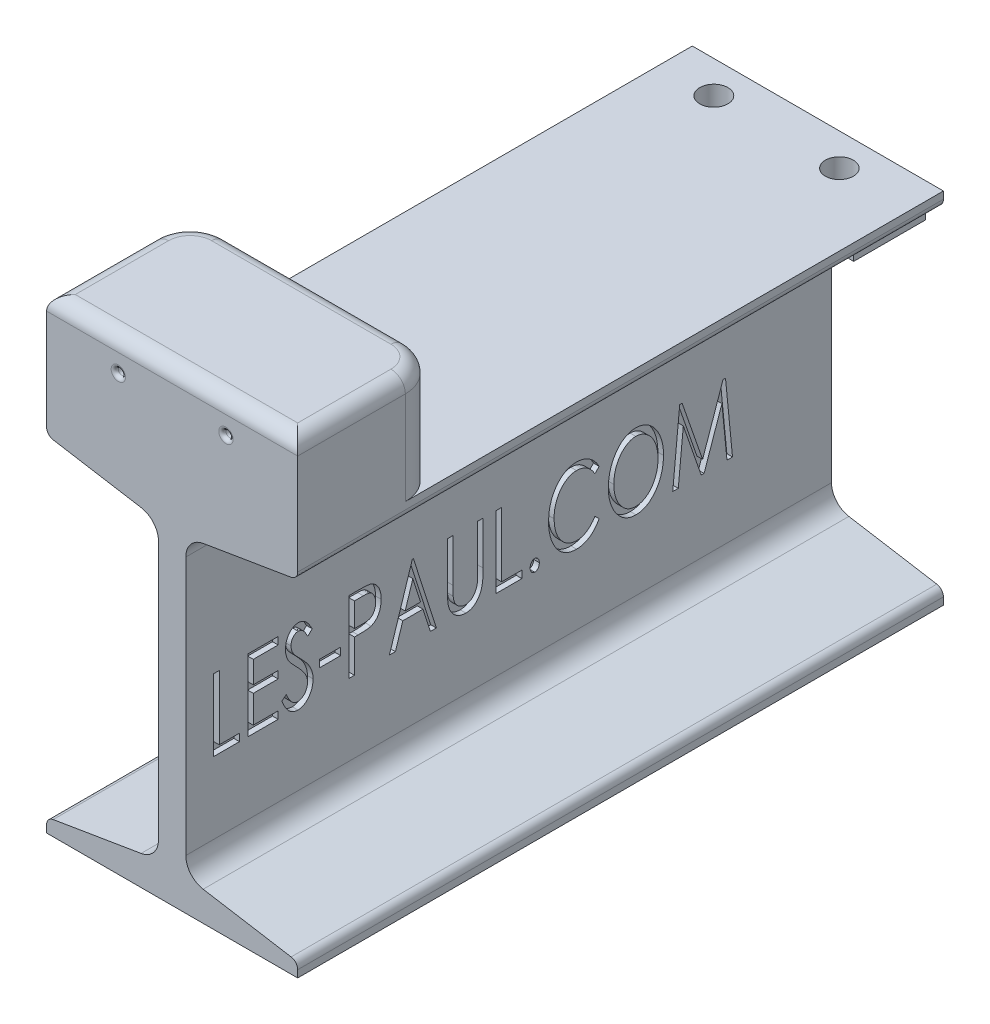
SolidWorks part; units mm, degrees
note: The reader was unsure of these and kept them because the rebuilt part matched: shared geometry of "Sketch47<4>".
material "AISI 1010 Steel, hot rolled bar"
ref_plane "Front Plane" through (0, 0, 0) normal (0, 0, 1) x (1, 0, 0)
ref_plane "Top Plane" through (0, 0, 0) normal (0, 1, 0) x (1, 0, 0)
ref_plane "Right Plane" through (0, 0, 0) normal (1, 0, 0) x (0, 0, -1)
sketch "Sketch1" plane through (0, 0, 0) normal (0, 0, 1) x (1, 0, 0)
  line L0 (0, -63.5) -> (0, 63.5) construction
  line L1 (-44.45, 63.5) -> (44.45, 63.5)
  line L2 (44.45, 63.5) -> (44.45, 60.96)
  line L3 (42.1152, 58.204) -> (10.9813, 53.0163)
  line L4 (4.826, 45.7505) -> (4.826, -45.7505)
  line L5 (10.9813, -53.0163) -> (42.1152, -58.204)
  line L6 (44.45, -60.96) -> (44.45, -63.5)
  line L7 (44.45, -63.5) -> (-44.45, -63.5)
  line L8 (-44.45, -60.96) -> (-44.45, -63.5)
  line L9 (-10.9813, -53.0163) -> (-42.1152, -58.204)
  line L10 (-4.826, 45.7505) -> (-4.826, -45.7505)
  line L11 (-42.1152, 58.204) -> (-10.9813, 53.0163)
  line L12 (-44.45, 63.5) -> (-44.45, 60.96)
  arc A0 (42.1152, -58.204) -> (44.45, -60.96) centre (41.656, -60.96) cw
  arc A1 (44.45, 60.96) -> (42.1152, 58.204) centre (41.656, 60.96) cw
  arc A2 (4.826, -45.7505) -> (10.9813, -53.0163) centre (12.192, -45.7505) ccw
  arc A3 (10.9813, 53.0163) -> (4.826, 45.7505) centre (12.192, 45.7505) ccw
  arc A4 (-10.9813, 53.0163) -> (-4.826, 45.7505) centre (-12.192, 45.7505) cw
  arc A5 (-4.826, -45.7505) -> (-10.9813, -53.0163) centre (-12.192, -45.7505) cw
  arc A6 (-44.45, 60.96) -> (-42.1152, 58.204) centre (-41.656, 60.96) ccw
  arc A7 (-42.1152, -58.204) -> (-44.45, -60.96) centre (-41.656, -60.96) ccw
  point P4 (0, 0)
  dimension "D3" = 2.794
  dimension "D4" = 7.366
  dimension "D1" = 127
  dimension "D2" = 44.45
  dimension "D5" = 9.46
  dimension "D6" = 9.46
  dimension "D7" = 2.54
  dimension "D8" = 2.54
  dimension "D9" = 4.826
extrude "Boss-Extrude1" add sketch "Sketch1" along normal mid plane 228.6
sketch "Sketch2" plane through (0, 63.5, 0) normal (0, 1, 0) x (1, 0, 0)
  line L0 (-44.45, -114.3) -> (-44.45, -63.5)
  line L1 (-44.45, -114.3) -> (-44.45, 114.3) construction
  line L2 (-44.45, -63.5) -> (44.45, -63.5)
  line L3 (44.45, -114.3) -> (44.45, 114.3) construction
  line L4 (44.45, -63.5) -> (44.45, -114.3)
  line L5 (44.45, -114.3) -> (-44.45, -114.3)
  dimension "D1" = 50.8
extrude "Boss-Extrude2" add sketch "Sketch2" along normal blind 38.1
fillet "Fillet4" radius 12.7 2 edges at (-44.45, 82.55, 63.5) (44.45, 82.55, 63.5)
fillet "Fillet5" radius 5.08 6 edges at (40.7303, 101.6, 67.2197) (0, 101.6, 63.5) (-40.7303, 101.6, 67.2197) (-44.45, 101.6, 95.25) (0, 101.6, 114.3) (44.45, 101.6, 95.25)
sketch "Sketch24" plane through (0, 0, 0) normal (0, 0, 1) x (1, 0, 0)
  line L0 (-10.9813, 53.0163) -> (-43.3872, 53.0163) construction
ref_plane "Plane2" through (0, 53.0163, 0) normal (0, 1, 0) x (1, 0, 0)
ref_plane "Plane4" through (0, -11.6213, 43.3713) normal (0, 0.2588, -0.9659) x (-1, 0, 0)
sketch "Sketch42" plane through (0, 141.2713, 63.5) normal (0, 0, 1) x (-1, 0, 0)
  line L0 (31.75, 44.7513) -> (-31.75, 44.7513) construction
  line L1 (44.45, 44.7513) -> (44.45, 77.7713) construction
  line L2 (0, 77.7713) -> (0, 44.7513) construction
  line L3 (-31.75, 77.7713) -> (31.75, 77.7713) construction
  circle A0 centre (19.05, 51.1013) radius 1.27
  circle A1 centre (-19.05, 51.1013) radius 1.27
  dimension "D1" = 2.54
  dimension "D3" = 6.35
  dimension "D2" = 25.4
extrude "Cut-Extrude3" cut sketch "Sketch42" against normal mid plane 177.8
fillet "Fillet8" radius 1.27 2 edges at (-20.32, 90.17, 114.3) (17.78, 90.17, 114.3)
sketch "Sketch45" plane through (0, 63.5, 0) normal (0, 1, 0) x (1, 0, 0)
  line L0 (-38.1, 114.3) -> (-38.1, 88.9)
  line L1 (44.45, 114.3) -> (-44.45, 114.3) construction
  line L2 (-38.1, 88.9) -> (38.1, 88.9)
  line L3 (38.1, 88.9) -> (38.1, 114.3)
  line L4 (38.1, 114.3) -> (-38.1, 114.3)
  line L5 (44.45, -76.2) -> (44.45, 114.3) construction
  line L6 (-44.45, -76.2) -> (-44.45, 114.3) construction
  dimension "D1" = 6.35
  dimension "D2" = 25.4
  dimension "D3" = 6.35
extrude "Boss-Extrude3" add sketch "Sketch45" against normal blind 12.065
sketch "Sketch47" plane through (0, 63.5, 0) normal (0, 1, 0) x (1, 0, 0)
  line L0 (0, 162.8047) -> (0, -29.721) construction
  line L1 (44.45, 114.3) -> (-44.45, 114.3) construction
  line L2 (-44.45, -76.2) -> (-44.45, 114.3) construction
  circle A0 centre (-25.4, 102.87) radius 5
  circle A2 centre (19.05, 102.87) radius 4.953
  dimension "D1" = 10
  dimension "D4" = 9.906
  dimension "D2" = 11.43
  dimension "D3" = 19.05
  dimension "D5" = 19.05
  dimension "D6" = 11.43
extrude "Cut-Extrude5" cut sketch "Sketch47" against normal up to surface (12.065 mm away) up to face at (22.8038, 51.435, -101.6)
sketch "Sketch51" plane through (4.826, 0, 0) normal (1, 0, 0) x (0, 0, -1)
  line L0 (-114.3, -45.7505) -> (-114.3, 45.7505) construction
  line L1 (-114.3, -45.7505) -> (114.3, -45.7505) construction
  text T0 "LES-PAUL.COM" font "Century Gothic" height 25.4
  dimension "D1" = 7.62
  dimension "D2" = 25.4
extrude "Cut-Extrude9" cut sketch "Sketch47<4>" against normal blind 25.4
sketch "Sketch47<4>" plane through (0, 63.5, 0) normal (0, 1, 0) x (1, 0, 0) same geometry as "Sketch47"
extrude "Cut-Extrude8" cut sketch "Sketch51" against normal blind 2
sketch "Sketch52" plane through (0, 51.435, 0) normal (0, -1, 0) x (1, 0, 0)
  line L0 (44.45, -114.3) -> (-44.45, -114.3) construction
  circle A0 centre (31.242, -102.87) radius 1.905
  circle A1 centre (19.05, -102.87) radius 4.953 construction
  dimension "D2" = 3.81
  dimension "D1" = 12.192
  dimension "D3" = 11.43
extrude "Cut-Extrude10" cut sketch "Sketch52" against normal blind 8.89
sketch "Sketch53" plane through (0, 51.435, 0) normal (0, -1, 0) x (1, 0, 0)
  line L0 (-7.5075, -114.3) -> (-38.1, -114.3) construction
  circle A0 centre (-13.208, -102.87) radius 1.905
  circle A1 centre (-25.4, -102.87) radius 5 construction
  dimension "D1" = 3.81
  dimension "D2" = 12.192
  dimension "D3" = 11.43
extrude "Cut-Extrude11" cut sketch "Sketch53" against normal blind 8.89
sketch "Sketch54" plane through (0, -63.5, 0) normal (0, -1, 0) x (1, 0, 0)
  line L0 (-44.45, 114.3) -> (44.45, 114.3) construction
  line L1 (-44.45, 114.3) -> (-44.45, -114.3) construction
  line L2 (-44.45, -114.3) -> (44.45, -114.3) construction
  line L3 (44.45, 114.3) -> (44.45, -114.3) construction
  line L4 (42.1152, 114.3) -> (42.1152, -114.3) construction
  circle A0 centre (-35.99, -104.3) radius 2
  circle A1 centre (-35.99, -78.3) radius 2
  circle A2 centre (-19.7, 104.3) radius 2
  circle A3 centre (-19.7, 78.3) radius 2
  circle A4 centre (33.6552, 104.3) radius 2
  circle A5 centre (33.6552, 78.3) radius 2
  circle A6 centre (19.7, -78.3) radius 2
  circle A7 centre (19.7, -104.3) radius 2
  point P16 (0, 0)
  point P17 (0, 0)
  point P18 (0, 0)
  point P21 (0, 0)
  point P22 (0, 0)
  point P23 (0, 0)
  point P32 (0, 0)
  dimension "D1" = 4
  dimension "D2" = 26
  dimension "D3" = 26
  dimension "D4" = 26
  dimension "D5" = 26
  dimension "D6" = 24.75
  dimension "D7" = 10
  dimension "D8" = 8.46
  dimension "D9" = 10
  dimension "D10" = 24.75
  dimension "D11" = 8.46
